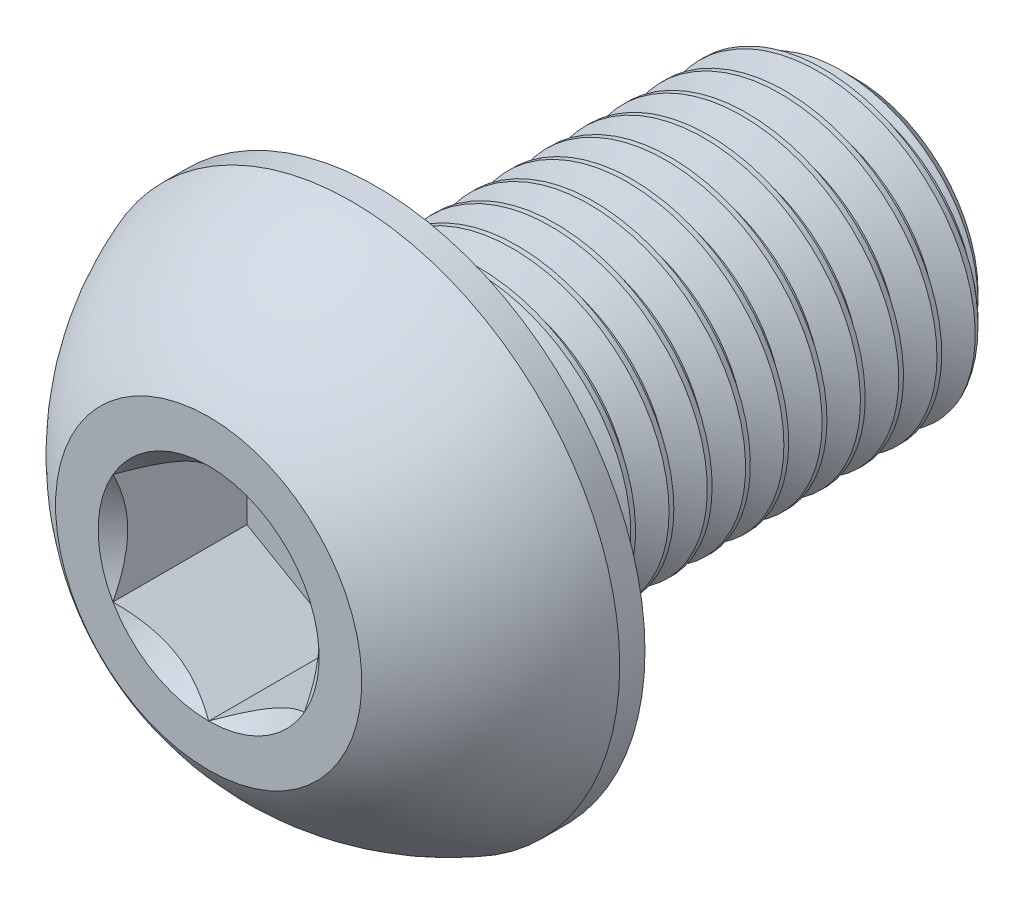
SolidWorks part; units mm, degrees
material "Alloy Steel"
ref_plane "Front Plane" through (0, 0, 0) normal (0, 0, 1) x (1, 0, 0)
ref_plane "Top Plane" through (0, 0, 0) normal (0, 1, 0) x (1, 0, 0)
ref_plane "Right Plane" through (0, 0, 0) normal (1, 0, 0) x (0, 0, -1)
sketch "Sketch1" plane through (0, 0, 0) normal (1, 0, 0) x (0, 0, -1)
  line L0 (-16.9, 0) -> (16.9, 0) construction
  line L1 (-8.1, 14) -> (-8.1, -14) construction
  line L2 (16.9, 8) -> (16.9, -8) construction
  line L3 (16.775, 8.2165) -> (17.775, 6.4845) construction
  line L4 (17.775, 6.4845) -> (18.775, 8.2165) construction
  line L5 (18.775, 8.2165) -> (16.775, 8.2165) construction
  line L6 (16.9, 8) -> (18.65, 8) construction
  line L7 (17.775, 8.2165) -> (17.775, 8) construction
  line L8 (17.775, 8) -> (17.775, 6.701) construction
  line L9 (17.775, 6.701) -> (17.775, 6.4845) construction
  line L10 (17.65, 6.701) -> (17.9, 6.701)
  line L11 (16.8375, 8.1083) -> (18.7125, 8.1083)
  line L12 (17.9, 6.701) -> (18.7125, 8.1083)
  line L13 (17.65, 6.701) -> (16.8375, 8.1083)
  line L14 (-16.9, 5) -> (-16.9, -5) construction
  line L15 (16.9, 8) -> (-8.1, 8) construction
  point P3 (-8.1, 0)
  point P6 (-9.9, 0)
  point P21 (17.775, 8.1083)
  point P24 (-9.42, 14)
  point P25 (11.9, -8)
  point P26 (-16.9, 8)
  dimension "Head Height" = 8.8
  dimension "Length" = 25
  dimension "Head Dia" = 28
  dimension "Thread Dia" = 16
  dimension "Pitch" = 2
  dimension "D2" = 0.25
  dimension "Drive Size" = 10
  dimension "D1" = 7
  dimension "D3" = 1.32
  dimension "D4" = 5
sketch "Sketch2" plane through (0, 0, 0) normal (1, 0, 0) x (0, 0, -1)
  line L0 (-16.9, 0) -> (16.9, 0)
  line L1 (16.9, 0) -> (16.9, 6.4)
  line L2 (16.9, 8) -> (16.9, -8) construction
  line L3 (16.9, 6.4) -> (15.3, 8)
  line L4 (15.3, 8) -> (-8.1, 8)
  line L5 (-8.1, 14) -> (-8.1, -14) construction
  line L6 (-8.1, 8) -> (-8.1, 14)
  line L7 (-8.1, 14) -> (-9.42, 14)
  line L8 (16.9, 8) -> (18.65, 8) construction
  line L9 (-16.9, 0) -> (-16.9, 8)
  arc A0 (-16.9, 8) -> (-9.42, 14) centre (-4.3365, 0) cw
  dimension "D1" = 1.6
  dimension "D2" = 45
revolve "Revolve1" add sketch "Sketch2" angle 360 about L0
sketch "Sketch3" plane through (0, 0, 16.9) normal (0, 0, 1) x (1, 0, 0)
  line L1 (0, 5.7735) -> (-5, 2.8868)
  line L2 (-5, 2.8868) -> (-5, -2.8868)
  line L3 (-5, -2.8868) -> (0, -5.7735)
  line L4 (0, -5.7735) -> (5, -2.8868)
  line L5 (5, -2.8868) -> (5, 2.8868)
  line L6 (5, 2.8868) -> (0, 5.7735)
  circle A0 centre (0, 0) radius 5 construction
  dimension "D1" = 10
extrude "Cut-Extrude1" cut sketch "Sketch3" against normal up to vertex (7 mm away) up to point (0, 0, 9.9)
sketch "Sketch4" plane through (0, 0, 16.9) normal (0, 0, 1) x (1, 0, 0)
  circle A0 centre (0, 0) radius 5.7735
extrude "Cut-Extrude2" cut sketch "Sketch4" against normal blind 10 draft 45
split "Split1" bodies to split 106 resulting bodies 107 108 split by face at (14, 0, 8.1)
sketch "Sketch5" plane through (0, 0, -16.9) normal (0, 0, -1) x (-1, 0, 0)
  circle A0 centre (0, 0) radius 8 construction
  circle A1 centre (0, 0) radius 8
curve "Helix/Spiral1" pitch 2 height 27 radius 8 centre (0, 0, -16.9) axis (0, 0, 1) start towards (0, 1, 0)
sketch "Sketch6" plane through (0, 0, 0) normal (1, 0, 0) x (0, 0, -1)
  line L0 (17.65, 6.701) -> (17.9, 6.701) construction
  line L1 (17.65, 6.701) -> (16.8375, 8.1083) construction
  line L2 (16.8375, 8.1083) -> (18.7125, 8.1083) construction
  line L3 (17.9, 6.701) -> (18.7125, 8.1083) construction
  line L4 (17.65, 6.701) -> (17.9, 6.701)
  line L5 (17.65, 6.701) -> (16.8375, 8.1083)
  line L6 (16.8375, 8.1083) -> (18.7125, 8.1083)
  line L7 (17.9, 6.701) -> (18.7125, 8.1083)
sweep "Cut-Sweep1" cut profiles "Sketch6" path "Helix/Spiral1" align with end faces yes
sketch "Sketch7" plane through (0, 0, 8.1) normal (0, 0, -1) x (-1, 0, 0)
  circle A1 centre (0, 0) radius 8
  circle A2 centre (0, 0) radius 8
  dimension "D1" = 0
extrude "Boss-Extrude1" add sketch "Sketch7" along normal blind 10 draft 30
equation "\"D2@Sketch1\" = \"Pitch@Sketch1\" / 8"
equation "\"D1@Sketch1\"=\"Drive Size@Sketch1\"*.7"
equation "\"D3@Sketch1\"=\"Head Height@Sketch1\"*.15"
equation "\"D1@Sketch2\"=\"Pitch@Sketch1\"*.8"
equation "\"D1@Sketch3\"=\"Drive Size@Sketch1\""
equation "\"D4@Helix/Spiral1\"=\"Pitch@Sketch1\""
equation "\"D3@Helix/Spiral1\"=\"Length@Sketch1\"+\"Pitch@Sketch1\""
equation "\"D4@Sketch1\"=\"Pitch@Sketch1\"*2.5"
